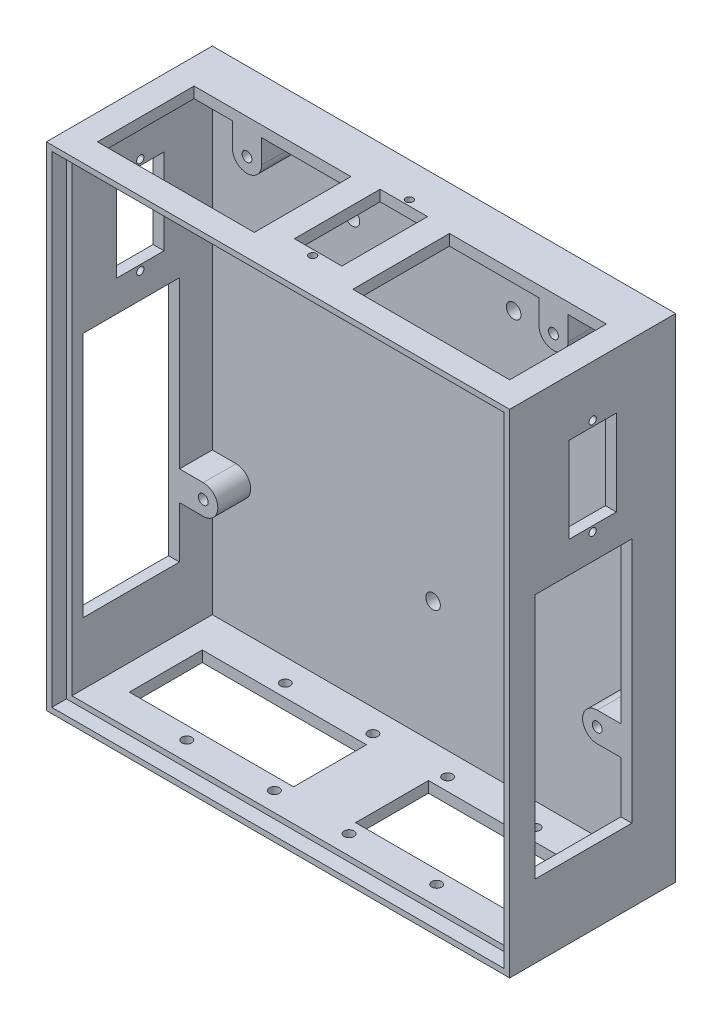
SolidWorks part; units mm, degrees
ref_plane "Front Plane" through (0, 0, 0) normal (0, 0, 1) x (1, 0, 0)
ref_plane "Top Plane" through (0, 0, 0) normal (0, 1, 0) x (1, 0, 0)
ref_plane "Right Plane" through (0, 0, 0) normal (1, 0, 0) x (0, 0, -1)
sketch "Sketch1" plane through (0, 0, 0) normal (0, 0, 1) x (1, 0, 0)
  line L1 (63.5, 67.5) -> (-63.5, 67.5)
  line L2 (63.5, 67.5) -> (63.5, -67.5)
  line L3 (63.5, -67.5) -> (-63.5, -67.5)
  line L4 (-63.5, 67.5) -> (-63.5, -67.5)
  line L5 (63.5, 67.5) -> (-63.5, -67.5) construction
  line L6 (63.5, -67.5) -> (-63.5, 67.5) construction
  point P0 (0, 0)
  dimension "D1" = 127
  dimension "D2" = 135
extrude "Boss-Extrude1" add sketch "Sketch1" along normal blind 45.5
sketch "Sketch2" plane through (0, 0, 45.5) normal (0, 0, 1) x (1, 0, 0)
  line L0 (-63.5, 67.5) -> (-63.5, -67.5) construction
  line L1 (60.5, 64.5) -> (-60.5, 64.5)
  line L2 (60.5, 64.5) -> (60.5, -64.5)
  line L3 (60.5, -64.5) -> (-60.5, -64.5)
  line L4 (-60.5, 64.5) -> (-60.5, -64.5)
  line L5 (60.5, 64.5) -> (-60.5, -64.5) construction
  line L6 (60.5, -64.5) -> (-60.5, 64.5) construction
  line L7 (63.5, 67.5) -> (-63.5, 67.5) construction
  line L9 (62, 66) -> (-62, 66)
  line L10 (62, 66) -> (62, -66)
  line L11 (62, -66) -> (-62, -66)
  line L12 (-62, 66) -> (-62, -66)
  line L13 (62, 66) -> (-62, -66) construction
  line L14 (62, -66) -> (-62, 66) construction
  point P0 (0, 0)
  point P10 (0, 0)
  dimension "D1" = 3
  dimension "D2" = 3
  dimension "D3" = 1.5
  dimension "D4" = 1.5
extrude "Cut-Extrude1" cut sketch "Sketch2" against normal offset from surface (42.5 mm away) 3 contours L1 L4 L3 L2 region at (0, 0, 45.5) up to face at (0, 0, 0)
extrude "Cut-Extrude2" cut sketch "Sketch2<3>" against normal blind 4
sketch "Sketch2<3>" plane through (0, 0, 45.5) normal (0, 0, 1) x (1, 0, 0) same geometry as "Sketch2"
sketch "Sketch3" plane through (0, 0, 3) normal (0, 0, 1) x (1, 0, 0)
  line L0 (38, 58) -> (38, 64.5)
  line L1 (60.5, 64.5) -> (-60.5, 64.5) construction
  line L2 (46, 58) -> (46, 64.5)
  line L3 (60.5, 64.5) -> (-60.5, 64.5) construction
  line L4 (0, -25.025) -> (0, 25.025) construction
  arc A0 (38, 58) -> (46, 58) centre (42, 58) ccw
  circle A2 centre (42, 58) radius 1.35
  line M3 (60.5, 64.5) -> (-60.5, 64.5)
  dimension "D2" = 4
  dimension "D3" = 2.7
  dimension "D1" = 6.5
  dimension "D4" = 42
extrude "Boss-Extrude2" add sketch "Sketch3" along normal blind 9 contours L0 A0 L2 A2 M3 region at (42, 59.7692, 3)
mirror "Mirror1" about plane through (0, 0, 0) normal (1, 0, 0) of "Boss-Extrude2"
sketch "Sketch4" plane through (0, 0, 3) normal (0, 0, 1) x (1, 0, 0)
  line L0 (54, -25.4) -> (60.5, -25.4)
  line L1 (60.5, 64.5) -> (60.5, -64.5) construction
  line L2 (54, -33.4) -> (60.5, -33.4)
  arc A0 (54, -25.4) -> (54, -33.4) centre (54, -29.4) ccw
  circle A1 centre (54, -29.4) radius 1.35
  circle A2 centre (42, 58) radius 1.35 construction
  line M9 (60.5, -64.5) -> (60.5, 64.5)
  dimension "D2" = 4
  dimension "D3" = 2.7
  dimension "D4" = 87.4
  dimension "D1" = 6.5
extrude "Boss-Extrude3" add sketch "Sketch4" along normal blind 9 contours L0 A0 L2 A1 M9 region at (55.7692, -29.4, 3)
mirror "Mirror2" about plane through (0, 0, 0) normal (1, 0, 0) of "Boss-Extrude3"
sketch "Sketch5" plane through (0, 67.5, 0) normal (0, 1, 0) x (1, 0, 0)
  line L0 (0, -22.75) -> (6.5, -22.75) construction
  line L1 (6.5, -11) -> (-6.5, -11)
  line L2 (6.5, -11) -> (6.5, -34.5)
  line L3 (6.5, -34.5) -> (-6.5, -34.5)
  line L4 (-6.5, -11) -> (-6.5, -34.5)
  line L5 (6.5, -11) -> (-6.5, -34.5) construction
  line L6 (6.5, -34.5) -> (-6.5, -11) construction
  line L7 (63.5, -45.5) -> (63.5, 0) construction
  circle A0 centre (0, -9.5) radius 1
  circle A1 centre (0, -36) radius 1
  point P0 (0, -22.75)
  point P8 (0, -11)
  point P12 (63.5, -22.75)
  dimension "D3" = 2
  dimension "D1" = 13
  dimension "D2" = 23.5
  dimension "D4" = 1.5
extrude "Cut-Extrude5" cut sketch "Sketch5" against normal up to surface (3 mm away) up to face at (0, 64.5, 12.4167)
sketch "Sketch7" plane through (63.5, 0, 0) normal (1, 0, 0) x (0, 0, -1)
  line L0 (-45.5, 67.5) -> (0, 67.5) construction
  line L1 (-16.25, 52) -> (-29.25, 52)
  line L2 (-16.25, 52) -> (-16.25, 28.5)
  line L3 (-16.25, 28.5) -> (-29.25, 28.5)
  line L4 (-29.25, 52) -> (-29.25, 28.5)
  line L5 (-16.25, 52) -> (-29.25, 28.5) construction
  line L6 (-16.25, 28.5) -> (-29.25, 52) construction
  line L8 (-22.75, 40.25) -> (-16.25, 40.25) construction
  circle A0 centre (-22.75, 53.5) radius 1
  circle A1 centre (-22.75, 27) radius 1
  point P0 (-22.75, 40.25)
  point P7 (-22.75, 67.5)
  dimension "D4" = 2
  dimension "D1" = 23.5
  dimension "D2" = 27.25
  dimension "D3" = 13
  dimension "D5" = 1.5
extrude "Cut-Extrude6" cut sketch "Sketch7" against normal up to surface (3 mm away) up to face at (60.5, -14.7, 14.875)
mirror "Mirror4" about plane through (0, 0, 0) normal (1, 0, 0) of "Cut-Extrude6"
sketch "Sketch8" plane through (0, -67.5, 0) normal (0, -1, 0) x (1, 0, 0)
  line L0 (-63.5, 45.5) -> (-63.5, 0) construction
  line L1 (-8.5, 32.75) -> (-53.5, 32.75)
  line L2 (-8.5, 32.75) -> (-8.5, 12.75)
  line L3 (-8.5, 12.75) -> (-53.5, 12.75)
  line L4 (-53.5, 32.75) -> (-53.5, 12.75)
  circle A2 centre (-10.25, 36.25) radius 1.35
  circle A3 centre (-34.25, 36.25) radius 1.35
  circle A4 centre (-34.25, 9.25) radius 1.35
  circle A5 centre (-10.25, 9.25) radius 1.35
  point P4 (-53.5, 22.75)
  point P8 (-63.5, 22.75)
  dimension "D4" = 2.7
  dimension "D1" = 8.5
  dimension "D2" = 45
  dimension "D3" = 20
  dimension "D5" = 1.75
  dimension "D6" = 24
  dimension "D7" = 3.5
  dimension "D8" = 3.5
extrude "Cut-Extrude7" cut sketch "Sketch8" against normal up to surface (3 mm away) up to face at (0, -64.5, 22.25)
mirror "Mirror5" about plane through (0, 0, 0) normal (1, 0, 0) of "Cut-Extrude7"
sketch "Sketch9" plane through (0, 0, 0) normal (0, 0, -1) x (-1, 0, 0)
  line L0 (-63.5, 67.5) -> (63.5, 67.5) construction
  circle A0 centre (-22.1, 48.945) radius 2
  circle A1 centre (0, -31.065) radius 2
  dimension "D1" = 4
  dimension "D4" = 80.01
  dimension "D2" = 18.555
  dimension "D3" = 22.1
extrude "Cut-Extrude8" cut sketch "Sketch9" against normal up to surface (3 mm away) up to face at (0, 12.34, 3)
mirror "Mirror6" about plane through (0, 0, 0) normal (1, 0, 0) of "Cut-Extrude8"
sketch "Sketch10" plane through (63.5, 0, 0) normal (1, 0, 0) x (0, 0, -1)
  line L0 (-45.5, -67.5) -> (0, -67.5) construction
  line L1 (-38.5, 20) -> (-12, 20)
  line L2 (-38.5, 20) -> (-38.5, -47.5)
  line L3 (-38.5, -47.5) -> (-12, -47.5)
  line L4 (-12, 20) -> (-12, -47.5)
  line L5 (-45.5, -67.5) -> (-45.5, 67.5) construction
  line L6 (-12, -33.4) -> (-12, -25.4) construction
  circle A0 centre (-22.75, 27) radius 1 construction
  dimension "D3" = 7
  dimension "D1" = 20
  dimension "D2" = 7
extrude "Cut-Extrude9" cut sketch "Sketch10" against normal up to surface (127 mm away) up to face at (-63.5, 0, 22.75)
sketch "Sketch11" plane through (0, 67.5, 0) normal (0, 1, 0) x (1, 0, 0)
  line L0 (63.5, -45.5) -> (63.5, 0) construction
  line L1 (13.5, -12) -> (56.5, -12)
  line L2 (13.5, -12) -> (13.5, -38.5)
  line L3 (13.5, -38.5) -> (56.5, -38.5)
  line L4 (56.5, -12) -> (56.5, -38.5)
  line L5 (63.5, -45.5) -> (-63.5, -45.5) construction
  line L6 (6.5, -34.5) -> (6.5, -11) construction
  line L7 (46, -12) -> (38, -12) construction
  dimension "D1" = 7
  dimension "D2" = 7
  dimension "D3" = 7
extrude "Cut-Extrude10" cut sketch "Sketch11" against normal up to surface (3 mm away) up to face at (0, 64.5, 37)
mirror "Mirror7" about plane through (0, 0, 0) normal (1, 0, 0) of "Cut-Extrude10"
